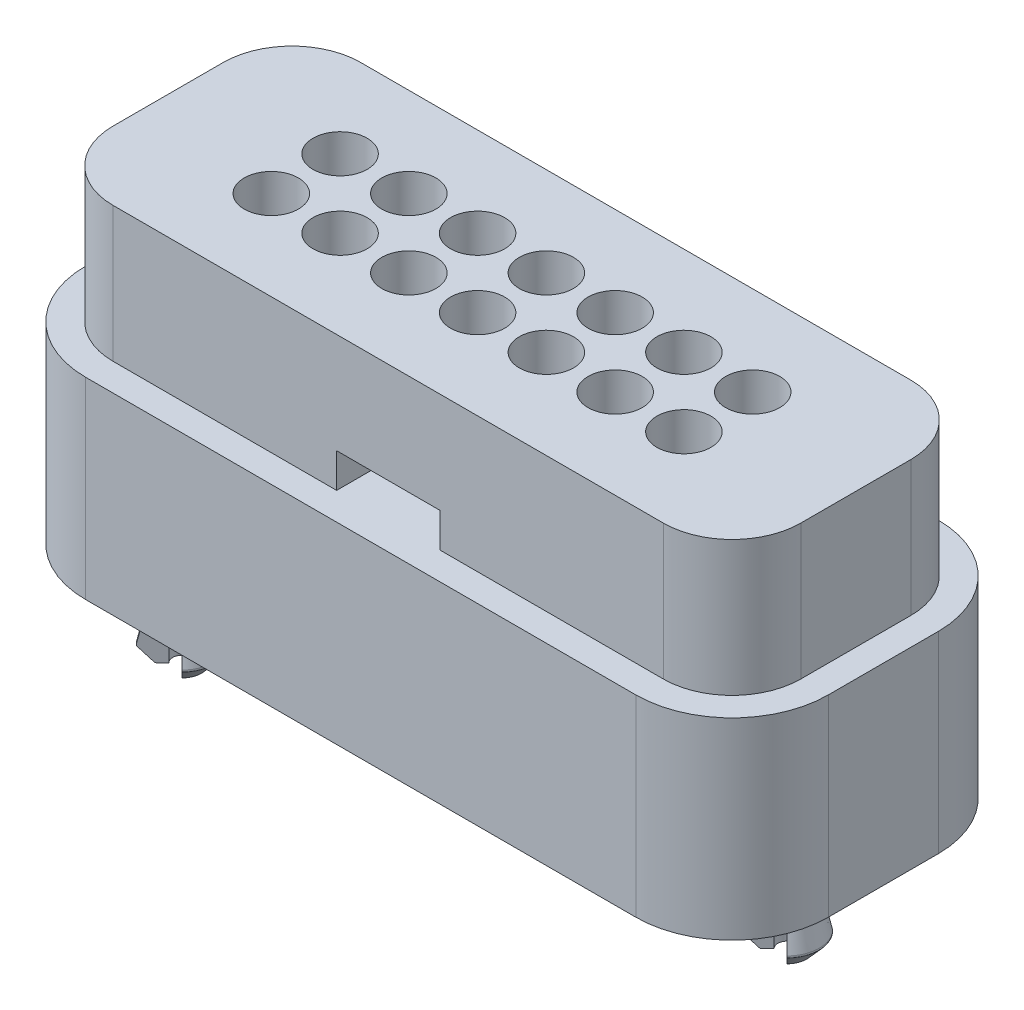
SolidWorks part; units mm, degrees
ref_plane "Front Plane" through (0, 0, 0) normal (0, 0, 1) x (1, 0, 0)
ref_plane "Top Plane" through (0, 0, 0) normal (0, 1, 0) x (1, 0, 0)
ref_plane "Right Plane" through (0, 0, 0) normal (1, 0, 0) x (0, 0, -1)
sketch "Sketch1" plane through (0, 0, 0) normal (0, 1, 0) x (1, 0, 0)
  line L0 (0, 0) -> (0, 1.27) construction
  line L1 (0, 0.635) -> (7.43, 0.635) construction
  line L2 (8.89, 0.635) -> (-1.27, 0.635) construction
  line L3 (-1.27, 3.429) -> (8.89, 3.429)
  line L4 (-1.27, -1.651) -> (8.89, -1.651)
  line L5 (-2.54, -0.381) -> (-2.54, 1.651)
  line L6 (-1.27, 2.921) -> (8.89, 2.921)
  line L7 (10.16, -0.381) -> (10.16, 1.651)
  line L8 (-2.54, -1.651) -> (10.16, 2.921) construction
  line L9 (-2.54, 2.921) -> (10.16, -1.651) construction
  line L10 (10.668, -0.381) -> (10.668, 1.651)
  line L11 (-1.27, -2.159) -> (8.89, -2.159)
  line L12 (-3.048, -0.381) -> (-3.048, 1.651)
  circle A0 centre (0, 0) radius 0.5
  circle A1 centre (1.27, 0) radius 0.5
  circle A2 centre (2.54, 0) radius 0.5
  circle A3 centre (3.81, 0) radius 0.5
  circle A4 centre (5.08, 0) radius 0.5
  circle A5 centre (6.35, 0) radius 0.5
  circle A6 centre (1.27, 1.27) radius 0.5
  circle A7 centre (2.54, 1.27) radius 0.5
  circle A8 centre (3.81, 1.27) radius 0.5
  circle A9 centre (5.08, 1.27) radius 0.5
  circle A10 centre (6.35, 1.27) radius 0.5
  circle A11 centre (0, 1.27) radius 0.5
  circle A12 centre (8.89, 0.635) radius 0.5
  circle A13 centre (-1.27, -0.381) radius 0.5
  circle A14 centre (-1.27, 1.651) radius 0.5
  arc A15 (-1.27, -1.651) -> (-2.54, -0.381) centre (-1.27, -0.381) cw
  arc A16 (8.89, -1.651) -> (10.16, -0.381) centre (8.89, -0.381) ccw
  arc A17 (8.89, 2.921) -> (10.16, 1.651) centre (8.89, 1.651) cw
  arc A18 (-2.54, 1.651) -> (-1.27, 2.921) centre (-1.27, 1.651) cw
  arc A19 (8.89, 3.429) -> (10.668, 1.651) centre (8.89, 1.651) cw
  arc A20 (8.89, -2.159) -> (10.668, -0.381) centre (8.89, -0.381) ccw
  arc A21 (-1.27, -2.159) -> (-3.048, -0.381) centre (-1.27, -0.381) cw
  arc A22 (-3.048, 1.651) -> (-1.27, 3.429) centre (-1.27, 1.651) cw
  circle A23 centre (7.62, 0) radius 0.5
  circle A24 centre (7.62, 1.27) radius 0.5
  point P28 (3.81, 0.635)
  point P63 (0, 0)
  point P68 (0, 0)
  point P69 (0, 0)
  dimension "D1" = 7
  dimension "D3" = 2.54
  dimension "D5" = 1.27
  dimension "D10" = 1.27
  dimension "D9" = 1.27
  dimension "D4" = 0.635
  dimension "D6" = 0.381
  dimension "D7" = 1.27
  dimension "D8" = 1.27
  dimension "D12" = 10.16
  dimension "D11" = 0.508
  dimension "D2" = 2
extrude "Boss-Extrude1" add sketch "Sketch1" along normal blind 6.05 contours A14 | A13 | A18 L5 A15 L4 A16 L7 A17 L6 A0 A1 A2 A3 A4 A5 A6 A7 A8 A9 A10 A11 A12 A13 A14 | A12 region at (3.9021, 0, -0.635) region at (8.89, 0, -0.635) region at (-1.27, 0, 0.381) region at (-1.27, 0, -1.651)
extrude "Boss-Extrude2" add sketch "Sketch1<3>" along normal blind 3.556 contours A22 L12 A21 L11 A20 L10 A19 L3 L5 A18 L6 A17 L7 A16 L4 A15 region at (3.81, 0, -3.2809)
sketch "Sketch1<3>" plane through (0, 0, 0) normal (0, 1, 0) x (1, 0, 0) same geometry as "Sketch1"
sketch "Sketch4" plane through (0, 0, 1.651) normal (0, 0, 1) x (1, 0, 0)
  line L0 (2.8575, 3.556) -> (4.7625, 3.556)
  line L2 (-1.27, 3.556) -> (8.89, 3.556) construction
  line L3 (2.8575, 3.556) -> (2.8575, 4.191)
  line L4 (2.8575, 4.191) -> (4.7625, 4.191)
  line L5 (4.7625, 4.191) -> (4.7625, 3.556)
  point P5 (3.81, 3.556)
  point P7 (3.175, 3.556)
  point P8 (0, 0)
extrude "Cut-Extrude1" cut sketch "Sketch4" against normal blind 0.635
sketch "Sketch5" plane through (0, 0, -2.921) normal (0, 0, 1) x (1, 0, 0)
  line L0 (2.8575, 3.556) -> (4.7625, 3.556)
  line L3 (2.8575, 3.556) -> (2.8575, 4.191)
  line L4 (2.8575, 4.191) -> (4.7625, 4.191)
  line L5 (4.7625, 4.191) -> (4.7625, 3.556)
  point P3 (0, 0)
  point P5 (3.81, 3.556)
extrude "Cut-Extrude2" cut sketch "Sketch5" along normal blind 0.635
fillet "Fillet1" radius 0.635 2 edges at (3.81, 4.191, 1.016) (3.81, 4.191, -2.286)
sketch3d "3DSketch1"
  line L0 (-1.27, 0, 0.381) -> (-1.27, -4.1645, 0.381) construction
  line L1 (-1.27, 0, -1.651) -> (-1.27, -1.854, -1.651) construction
  line L2 (8.89, 0, -0.635) -> (8.89, -2.1296, -0.635) construction
ref_plane "Plane1" through (0, 0, 0.381) normal (0, 0, 1) x (1, 0, 0)
ref_plane "Plane2" through (0, 0, -1.651) normal (0, 0, 1) x (1, 0, 0)
ref_plane "Plane3" through (0, 0, -0.635) normal (0, 0, 1) x (1, 0, 0)
sketch "Sketch6" plane through (0, 0, 0.381) normal (0, 0, 1) x (1, 0, 0)
  line L0 (-1.27, 0) -> (-0.7715, 0) construction
  line L1 (-0.67, 0) -> (-0.82, -0.96)
  line L2 (-0.82, -0.96) -> (-0.67, -1.6205)
  line L3 (-0.67, -1.6205) -> (-0.92, -1.9)
  line L4 (-0.92, -1.9) -> (-1.1, -1.9)
  line L5 (-1.1, -1.9) -> (-1.1, 0)
  line L6 (-1.27, 200000) -> (-1.27, -200004.1645) construction
  line L7 (-1.1, -0.95) -> (-1.27, -1.8847) construction
  line L8 (-1.27, -1.8847) -> (-1.0929, -1.9169) construction
  line L9 (-1.27, 0) -> (-1.27, -2.989) construction
  line L10 (-0.82, -0.96) -> (-0.843, -1.6369) construction
  line L11 (-1.0929, -1.9169) -> (-0.843, -1.6369) construction
  line L12 (-1.87, 0) -> (-1.72, -0.96)
  line L13 (-1.72, -0.96) -> (-1.87, -1.6205)
  line L14 (-1.44, -1.9) -> (-1.44, 0)
  line L15 (-1.87, -1.6205) -> (-1.62, -1.9)
  line L16 (-1.62, -1.9) -> (-1.44, -1.9)
  line L17 (-1.87, 0) -> (-1.44, 0)
  line L18 (-1.1, 0) -> (-0.67, 0)
  line L19 (-0.67, 0) -> (-0.6631, -0.0089)
  point P1 (-1.27, 0)
  point P5 (-0.67, 0)
  point P7 (-1.87, 0)
  dimension "D1" = 0.6
  dimension "D2" = 0.6
  dimension "D3" = 0.17
  dimension "D4" = 0.45
  dimension "D5" = 1.9
  dimension "D6" = 0.96
  dimension "D7" = 0.6
  dimension "D8" = 0.35
  dimension "D9" = 90
  dimension "D10" = 0.6769
  dimension "D11" = 0.3753
revolve "Revolve1" add sketch "Sketch6" angle 90 mid plane about L9 region at (-0.9223, -0.9212, 0.381) region at (-1.6177, -0.9212, 0.381)
sketch "Sketch7" plane through (0, 0, -1.651) normal (0, 0, 1) x (1, 0, 0)
  line L0 (-1.27, 0) -> (-0.7715, 0) construction
  line L1 (-0.67, 0) -> (-0.82, -0.96)
  line L2 (-0.82, -0.96) -> (-0.67, -1.6205)
  line L3 (-0.67, -1.6205) -> (-0.92, -1.9)
  line L4 (-0.92, -1.9) -> (-1.1, -1.9)
  line L5 (-1.1, -1.9) -> (-1.1, 0)
  line L7 (-1.1, -0.95) -> (-1.27, -1.8847) construction
  line L8 (-1.27, -1.8847) -> (-1.0929, -1.9169) construction
  line L9 (-1.27, 0) -> (-1.27, -2.989) construction
  line L10 (-0.82, -0.96) -> (-0.843, -1.6369) construction
  line L11 (-1.0929, -1.9169) -> (-0.843, -1.6369) construction
  line L12 (-1.87, 0) -> (-1.72, -0.96)
  line L13 (-1.72, -0.96) -> (-1.87, -1.6205)
  line L14 (-1.44, -1.9) -> (-1.44, 0)
  line L15 (-1.87, -1.6205) -> (-1.62, -1.9)
  line L16 (-1.62, -1.9) -> (-1.44, -1.9)
  line L17 (-1.87, 0) -> (-1.44, 0)
  line L18 (-1.1, 0) -> (-0.67, 0)
  line L19 (-0.67, 0) -> (-0.6631, -0.0089)
  point P1 (-1.27, 0)
  point P5 (-0.67, 0)
  point P7 (-1.87, 0)
  dimension "D1" = 0.6
  dimension "D2" = 0.6
  dimension "D5" = 1.9
  dimension "D6" = 0.96
  dimension "D9" = 90
  dimension "D10" = 0.6769
  dimension "D11" = 0.3753
sketch "Sketch8" plane through (0, 0, -0.635) normal (0, 0, 1) x (1, 0, 0)
  line L0 (8.89, 0) -> (9.3885, 0) construction
  line L1 (9.49, 0) -> (9.34, -0.96)
  line L2 (9.34, -0.96) -> (9.49, -1.6205)
  line L3 (9.49, -1.6205) -> (9.24, -1.9)
  line L4 (9.24, -1.9) -> (9.06, -1.9)
  line L5 (9.06, -1.9) -> (9.06, 0)
  line L7 (9.06, -0.95) -> (8.89, -1.8847) construction
  line L8 (8.89, -1.8847) -> (9.0671, -1.9169) construction
  line L9 (8.89, 0) -> (8.89, -2.989) construction
  line L10 (9.34, -0.96) -> (9.317, -1.6369) construction
  line L11 (9.0671, -1.9169) -> (9.317, -1.6369) construction
  line L12 (8.29, 0) -> (8.44, -0.96)
  line L13 (8.44, -0.96) -> (8.29, -1.6205)
  line L14 (8.72, -1.9) -> (8.72, 0)
  line L15 (8.29, -1.6205) -> (8.54, -1.9)
  line L16 (8.54, -1.9) -> (8.72, -1.9)
  line L17 (8.29, 0) -> (8.72, 0)
  line L18 (9.06, 0) -> (9.49, 0)
  line L19 (9.49, 0) -> (9.4969, -0.0089)
  point P1 (8.89, 0)
  point P5 (9.49, 0)
  point P7 (8.29, 0)
  dimension "D5" = 1.9
  dimension "D6" = 0.96
  dimension "D9" = 90
  dimension "D10" = 0.6769
  dimension "D11" = 0.3753
revolve "Revolve2" add sketch "Sketch8" angle 90 mid plane about L9 region at (9.2377, -0.9212, -0.635) region at (8.5423, -0.9212, -0.635)
revolve "Revolve3" add sketch "Sketch7" angle 90 mid plane about L9 region at (-0.9223, -0.9212, -1.651) region at (-1.6177, -0.9212, -1.651)
fillet "Fillet2" radius 0.35 6 edges at (-0.67, 0, 0.381) (-1.87, 0, 0.381) (-1.87, 0, -1.651) (-0.67, 0, -1.651) (8.29, 0, -0.635) (9.49, 0, -0.635)
fillet "Fillet3" radius 0.05 18 edges at (9.49, -1.6205, -0.635) (9.24, -1.9, -0.635) (8.29, -1.6205, -0.635) (8.54, -1.9, -0.635) (-0.67, -1.6205, -1.651) (-0.92, -1.9, -1.651) (-1.62, -1.9, -1.651) (-1.87, -1.6205, -1.651) (-1.87, -1.6205, 0.381) (-1.62, -1.9, 0.381) (-0.92, -1.9, 0.381) (-0.67, -1.6205, 0.381) (-0.82, -0.96, 0.381) (-0.82, -0.96, -1.651) (-1.72, -0.96, 0.381) (-1.72, -0.96, -1.651) (8.44, -0.96, -0.635) (9.34, -0.96, -0.635)
